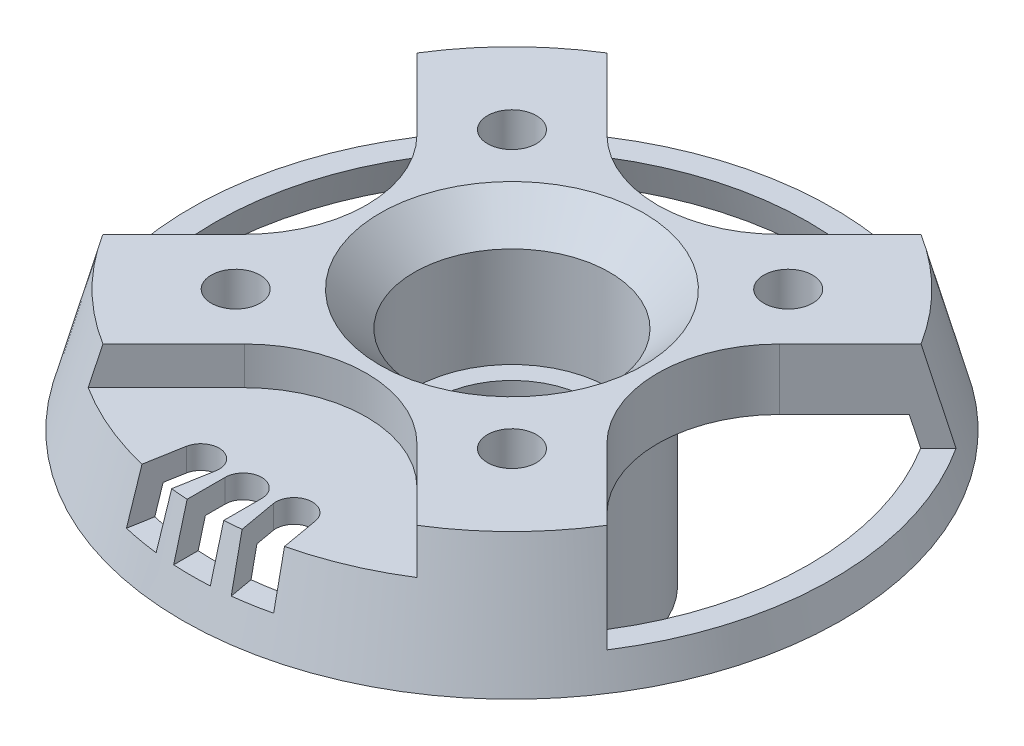
SolidWorks part; units mm, degrees
ref_plane "Front Plane" through (0, 0, 0) normal (0, 0, 1) x (1, 0, 0)
ref_plane "Top Plane" through (0, 0, 0) normal (0, 1, 0) x (1, 0, 0)
ref_plane "Right Plane" through (0, 0, 0) normal (1, 0, 0) x (0, 0, -1)
sketch "Sketch1" plane through (0, 0, 0) normal (0, 1, 0) x (1, 0, 0)
  circle A0 centre (0, 0) radius 13.5
  dimension "D1" = 27
extrude "Base size" add sketch "Sketch1" along normal blind 5
sketch "Sketch2" plane through (0, 5, 0) normal (0, 1, 0) x (1, 0, 0)
  line L0 (-9.5459, -9.5459) -> (9.5459, 9.5459) construction
  line L1 (-13.5, 0) -> (13.5, 0) construction
  line L2 (-9.5459, 9.5459) -> (9.5459, -9.5459) construction
  line L3 (0, 13.5) -> (0, -13.5) construction
  circle A0 centre (0, 0) radius 13.5 construction
  circle A1 centre (5.6569, 5.6569) radius 1
  circle A2 centre (-5.6569, -5.6569) radius 1
  circle A3 centre (5.6569, -5.6569) radius 1
  circle A4 centre (-5.6569, 5.6569) radius 1
  dimension "D2" = 2
  dimension "D1" = 45
  dimension "D3" = 16
extrude "Mounting holes" cut sketch "Sketch2" against normal up to next
sketch "Sketch3" plane through (0, 0, 0) normal (0, -1, 0) x (1, 0, 0)
  circle A0 centre (0, 0) radius 12.5
  circle A1 centre (0, 0) radius 13.5 construction
  dimension "D1" = 1
extrude "Rotor pocket" cut sketch "Sketch3" against normal blind 2.5 draft 15
chamfer "Outside chamfer" distance 5 angle 15 1 edges at (0, 5, 13.5) first distance on face at (0, 5, 13.5)
sketch "Sketch4" plane through (0, 5, 0) normal (0, 1, 0) x (1, 0, 0)
  line L0 (-8.5986, 8.5986) -> (8.5986, -8.5986) construction
  line L1 (-5.6569, 5.6569) -> (5.6569, 5.6569) construction
  line L2 (0, 12.1603) -> (0, -12.1603) construction
  line L3 (-12.1603, 0) -> (12.1603, 0) construction
  line L4 (-8.5986, -8.5986) -> (8.5986, 8.5986) construction
  line L5 (-10.5431, 6.6541) -> (6.6541, -10.5431)
  line L6 (-6.6541, -10.5431) -> (10.5431, 6.6541)
  line L7 (-6.6541, 10.5431) -> (10.5431, -6.6541)
  line L8 (-10.5431, -6.6541) -> (6.6541, 10.5431)
  line L9 (-10.5431, 6.6541) -> (-11.2903, 7.4012)
  line L10 (-6.6541, 10.5431) -> (-7.4012, 11.2903)
  line L11 (6.6541, 10.5431) -> (7.4012, 11.2903)
  line L12 (10.5431, 6.6541) -> (11.2903, 7.4012)
  line L13 (10.5431, -6.6541) -> (11.2903, -7.4012)
  line L14 (6.6541, -10.5431) -> (7.4012, -11.2903)
  line L15 (-6.6541, -10.5431) -> (-7.4012, -11.2903)
  line L16 (-10.5431, -6.6541) -> (-11.2903, -7.4012)
  circle A0 centre (0, 0) radius 12.1603 construction
  circle A1 centre (0, 0) radius 13.5
  circle A2 centre (0, 0) radius 13.5 construction
  circle M9 centre (0, 0) radius 12.1603
  dimension "D1" = 2.75
  dimension "D2" = 2.75
extrude "Bottom pockets top" cut sketch "Sketch4" against normal blind 1.55 contours L8 L5 M9 | L9 A1 L16 L8 L5 M9 | L7 L8 M9 | L11 A1 L10 L7 L8 M9 | L6 L7 M9 | L13 A1 L12 L6 L7 M9 | L15 A1 L14 L5 L6 M9 | L6 L5 M9 region at (-12.1626, 5, 0) region at (-8.9824, 5, 0) region at (0, 5, -8.9824) region at (0, 5, -12.1626) region at (0, 5, 8.9824) region at (0, 5, 12.1626) region at (8.9824, 5, 0) region at (12.1626, 5, 0)
sketch "Sketch5" plane through (0, 3.45, 0) normal (0, 1, 0) x (1, 0, 0)
  line L0 (-11.2903, 7.4012) -> (7.4012, -11.2903)
  line L1 (-10.3204, 6.4313) -> (-3.8891, 0) construction
  line L2 (7.4012, 11.2903) -> (-11.2903, -7.4012)
  line L3 (-10.3204, -6.4313) -> (-3.8891, 0) construction
  line L4 (-7.4012, 11.2903) -> (11.2903, -7.4012)
  line L5 (-6.4313, 10.3204) -> (0, 3.8891) construction
  line L6 (-7.4012, -11.2903) -> (11.2903, 7.4012)
  line L7 (3.8891, 0) -> (10.6216, 6.7325) construction
  circle A0 centre (0, 0) radius 13.5
  circle A1 centre (0, 0) radius 13.5 construction
  line M5 (-10.6216, -6.7325) -> (-3.8891, 0)
  line M6 (-3.8891, 0) -> (-10.6216, 6.7325)
  arc M7 (-10.6216, 6.7325) -> (-10.6216, -6.7325) centre (0, 0) ccw
extrude "Bottom pockets bottom" cut sketch "Sketch5" against normal offset from surface (2.15 mm away) 1.3 contours M7 M5 M6 | L0 A0 L2 M7 | L2 A0 L4 | L4 A0 L6 region at (-11.0626, 3.45, -6.9602) region at (-9.2333, 3.45, 0) region at (0, 3.45, -9.7912) region at (9.7912, 3.45, 0) up to face at (0, 0, -12.5)
fillet "Bottom pockets fillet" radius 5 4 edges at (0, 4.225, 3.8891) (3.8891, 3.75, 0) (0, 3.75, -3.8891) (-3.8891, 3.75, 0)
sketch "Sketch6" plane through (0, 5, 0) normal (0, 1, 0) x (1, 0, 0)
  circle A0 centre (0, 0) radius 4
  dimension "D1" = 8
extrude "Cut-Extrude5" cut sketch "Sketch6" against normal up to next
chamfer "Chamfer2" distance 1.4 angle 45 1 edges at (0, 5, 4)
sketch "Sketch7" plane through (0, 2.5, 0) normal (0, -1, 0) x (1, 0, 0)
  circle A0 centre (0, 0) radius 4
  circle A1 centre (0, 0) radius 4.8
  circle A2 centre (0, 0) radius 4 construction
  dimension "D1" = 0.8
extrude "Bearing bottom" add sketch "Sketch7" along normal blind 3
sketch "Sketch8" plane through (0, -0.5, 0) normal (0, -1, 0) x (1, 0, 0)
  circle A0 centre (0, 0) radius 4.8 construction
  circle A1 centre (0, 0) radius 4.8
  circle A2 centre (0, 0) radius 3.2
  circle A3 centre (0, 0) radius 4 construction
  dimension "D1" = 0.8
extrude "Bearing separator" add sketch "Sketch8" along normal blind 1
sketch "Sketch9" plane through (0, -1.5, 0) normal (0, -1, 0) x (1, 0, 0)
  circle A0 centre (0, 0) radius 4.8 construction
  circle A1 centre (0, 0) radius 4.8
  circle A2 centre (0, 0) radius 4 construction
  circle A3 centre (0, 0) radius 4
extrude "Bearing top" add sketch "Sketch9" along normal blind 4
sketch "Sketch10" plane through (0, 3.45, 0) normal (0, 1, 0) x (1, 0, 0)
  line L0 (0, -13.5) -> (0, 13.5) construction
  line L1 (0, 0) -> (0, -11) construction
  line L2 (0, 0) -> (-1.9101, -10.8329) construction
  line L3 (-2.6439, -10.6775) -> (-3.0788, -13.1442)
  line L4 (-1.1675, -10.9379) -> (-1.6025, -13.4046)
  line L5 (-0.75, -11) -> (-0.75, -13.4792)
  line L6 (2.6439, -10.6775) -> (3.0788, -13.1442)
  line L7 (1.1675, -10.9379) -> (1.6025, -13.4046)
  line L8 (0.75, -11) -> (0.75, -13.4792)
  circle A0 centre (0, 0) radius 11
  circle A1 centre (0, 0) radius 13.5 construction
  circle A2 centre (0, -11) radius 0.75
  circle A3 centre (-1.9101, -10.8329) radius 0.75
  circle A4 centre (1.9101, -10.8329) radius 0.75
  circle A5 centre (0, 0) radius 13.5
  arc M11 (-6.7325, -10.6216) -> (6.7325, -10.6216) centre (0, 0) ccw
  dimension "D1" = 2.5
  dimension "D2" = 1.5
  dimension "D4" = 10
  dimension "D3" = 2
extrude "Cut-Extrude6" cut sketch "Sketch10" against normal offset from surface (2.05 mm away) 1.4 contours A0 A3 | L3 A3 L4 A0 | A3 L3 L4 M11 | L3 A5 L4 M11 | L5 A5 L8 M11 | A2 L5 L8 M11 | A2 A0 | A0 A2 | A4 A0 | A4 L6 A0 L7 | L6 A4 L7 M11 | L7 A5 L6 M11 region at (-1.9646, 3.45, 11.1418) region at (-1.8541, 3.45, 10.5149) region at (-2.095, 3.45, 11.8813) region at (-2.2627, 3.45, 12.8326) region at (1.9646, 3.45, 11.1418) region at (1.8541, 3.45, 10.5149) region at (0, 3.45, 10.6771) region at (0, 3.45, 11.3137) region at (2.095, 3.45, 11.8813) region at (0, 3.45, 12.0643) region at (0, 3.45, 13.0306) region at (2.2627, 3.45, 12.8326) up to face at (0, 0, -12.5)
